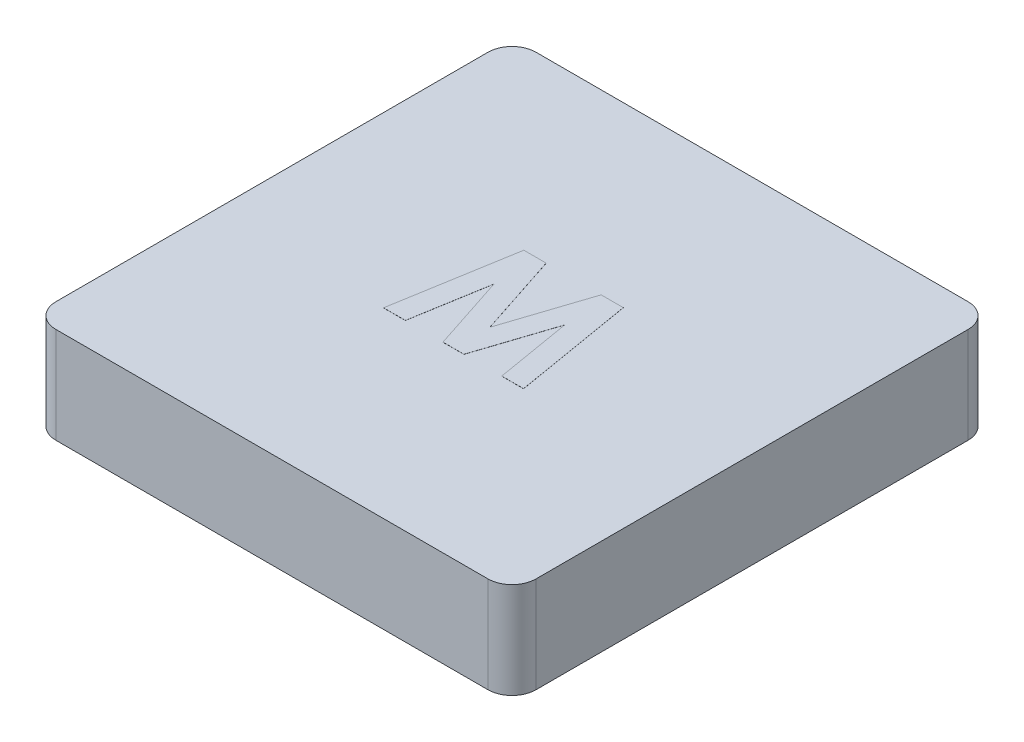
SolidWorks part; units mm, degrees
ref_plane "Front Plane" through (0, 0, 0) normal (0, 0, 1) x (1, 0, 0)
ref_plane "Top Plane" through (0, 0, 0) normal (0, 1, 0) x (1, 0, 0)
ref_plane "Right Plane" through (0, 0, 0) normal (1, 0, 0) x (0, 0, -1)
sketch "Sketch1" plane through (0, 0, 0) normal (0, 1, 0) x (1, 0, 0)
  line L0 (0, 0) -> (12.7, 0)
  line L1 (12.7, 0) -> (12.7, 12.7)
  line L2 (12.7, 12.7) -> (0, 12.7)
  line L3 (0, 12.7) -> (0, 0)
  dimension "D1" = 12.7
  dimension "D2" = 12.7
extrude "Boss-Extrude1" add sketch "Sketch1" along normal blind 2.54
fillet "Fillet1" radius 0.635 4 edges at (0, 1.27, -12.7) (12.7, 1.27, -12.7) (12.7, 1.27, 0) (0, 1.27, 0)
shell "Shell1" thickness 0.635 removed face at (6.35, 0, -6.35)
sketch "Sketch2" plane through (0, 1.905, 0) normal (0, -1, 0) x (-1, 0, 0)
  line L0 (-0.635, 6.35) -> (-12.065, 6.35) construction
  line L1 (-0.635, 12.065) -> (-0.635, 0.635) construction
  line L2 (-12.065, 0.635) -> (-12.065, 12.065) construction
  line L3 (-6.35, 0.635) -> (-6.35, 12.065) construction
  line L4 (-0.635, 0.635) -> (-12.065, 0.635) construction
  line L5 (-12.065, 12.065) -> (-0.635, 12.065) construction
  circle A0 centre (-6.35, 6.35) radius 2.54
  dimension "D1" = 5.08
extrude "Boss-Extrude2" add sketch "Sketch2" along normal up to surface (1.905 mm away) up to face at (6.35, 0, -6.35)
sketch "Sketch3" plane through (0, 2.54, 0) normal (0, 1, 0) x (1, 0, 0)
  line L0 (0, 12.065) -> (0, 0.635) construction
  line L1 (0.635, 0) -> (12.065, 0) construction
  text T0 "<b>M</b>"
  point P1 (0, 0)
  dimension "D1" = 4.3942
  dimension "D2" = 4.826
extrude "Boss-Extrude3" add sketch "Sketch3" along normal blind 0.0025
